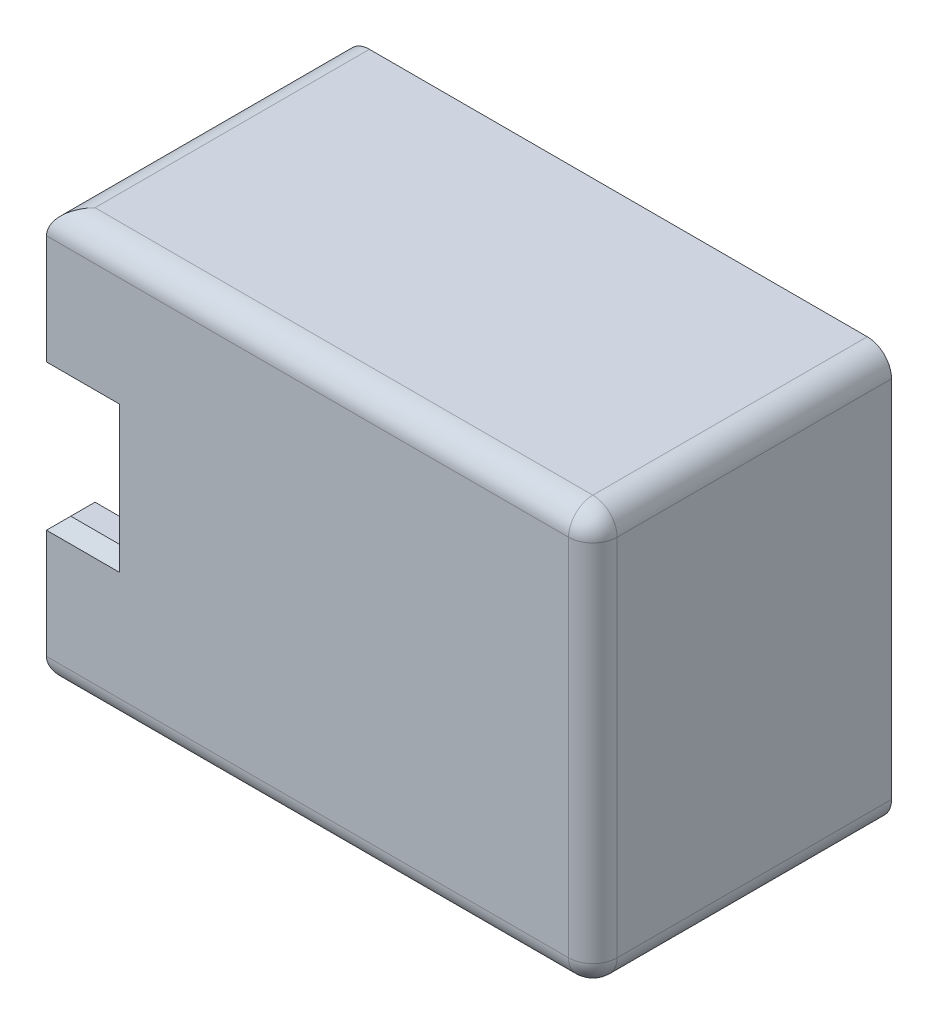
SolidWorks part; units mm, degrees
note: The reader was unsure of these and kept them because the rebuilt part matched: shared geometry of "Sketch1<3>", "Sketch4<4>".
ref_plane "Front Plane" through (0, 0, 0) normal (0, 0, 1) x (1, 0, 0)
ref_plane "Top Plane" through (0, 0, 0) normal (0, 1, 0) x (1, 0, 0)
ref_plane "Right Plane" through (0, 0, 0) normal (1, 0, 0) x (0, 0, -1)
sketch "Sketch1" plane through (0, 0, 0) normal (0, 0, 1) x (1, 0, 0)
  line L0 (-28.575, 17.78) -> (24.765, 17.78)
  line L1 (28.575, -21.59) -> (-28.575, -21.59)
  line L2 (28.575, -21.59) -> (28.575, 21.59)
  line L3 (28.575, 21.59) -> (-28.575, 21.59)
  line L4 (-28.575, -21.59) -> (-28.575, 21.59)
  line L5 (28.575, -21.59) -> (-28.575, 21.59) construction
  line L6 (28.575, 21.59) -> (-28.575, -21.59) construction
  line L7 (24.765, 17.78) -> (24.765, -17.78)
  line L8 (24.765, -17.78) -> (-28.575, -17.78)
  line L9 (-28.575, 10.16) -> (17.145, 10.16)
  line L10 (17.145, 10.16) -> (17.145, -10.16)
  line L11 (17.145, -10.16) -> (-28.575, -10.16)
  point P0 (0, 0)
  dimension "D1" = 57.15
  dimension "D2" = 43.18
  dimension "D3" = 53.34
  dimension "D4" = 35.56
  dimension "D5" = 3.81
  dimension "D6" = 45.72
  dimension "D7" = 20.32
  dimension "D8" = 7.62
extrude "Boss-Extrude1" add sketch "Sketch1" along normal blind 27.432 contours L7 L8 L4 L1 L2 L3 L0
extrude "Boss-Extrude2" add sketch "Sketch1<3>" along normal blind 5.08 contours L10 L11 L4 L8 L7 L0 L9
sketch "Sketch1<3>" plane through (0, 0, 0) normal (0, 0, 1) x (1, 0, 0) same geometry as "Sketch1"
sketch "Sketch4" plane through (0, 0, 5.08) normal (0, 0, 1) x (1, 0, 0)
  line L0 (-28.575, 17.78) -> (24.765, 17.78) construction
  line L1 (-20.6559, 17.78) -> (-23.7941, 17.78)
  line L2 (-23.7941, 17.78) -> (-25.3632, 15.0622)
  line L3 (-25.3632, 15.0622) -> (-23.7941, 12.3444)
  line L4 (-23.7941, 12.3444) -> (-20.6559, 12.3444)
  line L5 (-20.6559, 12.3444) -> (-19.0868, 15.0622)
  line L6 (-19.0868, 15.0622) -> (-20.6559, 17.78)
  line L7 (-28.575, 10.16) -> (-28.575, 17.78) construction
  line L8 (-2.54, 22.7847) -> (-2.54, -11.3368) construction
  line L9 (18.7141, 12.3444) -> (15.5759, 12.3444)
  line L10 (15.5759, 12.3444) -> (14.0068, 15.0622)
  line L11 (14.0068, 15.0622) -> (15.5759, 17.78)
  line L12 (15.5759, 17.78) -> (18.7141, 17.78)
  line L13 (18.7141, 17.78) -> (20.2832, 15.0622)
  line L14 (20.2832, 15.0622) -> (18.7141, 12.3444)
  line L15 (0, 0) -> (10.9329, 0) construction
  line L16 (20.2832, -15.0622) -> (18.7141, -12.3444)
  line L17 (18.7141, -17.78) -> (20.2832, -15.0622)
  line L18 (15.5759, -17.78) -> (18.7141, -17.78)
  line L19 (14.0068, -15.0622) -> (15.5759, -17.78)
  line L20 (15.5759, -12.3444) -> (14.0068, -15.0622)
  line L21 (18.7141, -12.3444) -> (15.5759, -12.3444)
  line L22 (-25.3632, -15.0622) -> (-23.7941, -12.3444)
  line L23 (-23.7941, -17.78) -> (-25.3632, -15.0622)
  line L24 (-19.0868, -15.0622) -> (-20.6559, -17.78)
  line L25 (-20.6559, -12.3444) -> (-19.0868, -15.0622)
  line L26 (-23.7941, -12.3444) -> (-20.6559, -12.3444)
  line L27 (-20.6559, -17.78) -> (-23.7941, -17.78)
  circle A0 centre (-22.225, 15.0622) radius 2.7178 construction
  circle A1 centre (-22.225, 15.0622) radius 1.524
  circle A2 centre (17.145, 15.0622) radius 1.524
  circle A3 centre (-22.225, -15.0622) radius 1.524
  circle A4 centre (17.145, -15.0622) radius 1.524
  dimension "D4" = 3.048
  dimension "D1" = 5.4356
  dimension "D2" = 6.35
  dimension "D3" = 2.54
extrude "Cut-Extrude1" cut sketch "Sketch4" against normal blind 2.286 contours L5 L6 L14 L2 L3 L4 A1 | L14 L13 L11 L10 L9 A2 | L26 L22 L23 L12 L24 L25 A3 | L16 L21 L20 L19 L12 L17 A4
extrude "Cut-Extrude2" cut sketch "Sketch4<4>" against normal through all contours A1 | A2 | A3 | A4
sketch "Sketch4<4>" plane through (0, 0, 5.08) normal (0, 0, 1) x (1, 0, 0) same geometry as "Sketch4"
sketch "Sketch7" plane through (0, 0, 27.432) normal (0, 0, 1) x (1, 0, 0)
  line L0 (0, 0) -> (-22.225, 0) construction
  line L1 (-28.575, 21.59) -> (28.575, 21.59)
  line L2 (-28.575, 21.59) -> (-28.575, 6.35)
  line L3 (-28.575, -21.59) -> (28.575, -21.59)
  line L4 (28.575, 21.59) -> (28.575, -21.59)
  line L5 (-28.575, 6.35) -> (-22.225, 6.35)
  line L7 (-28.575, -6.35) -> (-22.225, -6.35)
  line L8 (-22.225, 6.35) -> (-22.225, -6.35)
  line L9 (-28.575, -6.35) -> (-28.575, -21.59)
  line L10 (-28.575, 0) -> (-1035.3573, 0) construction
  point P11 (-22.225, 0)
  dimension "D1" = 12.7
  dimension "D2" = 6.35
extrude "Boss-Extrude3" add sketch "Sketch7" along normal blind 3.81
fillet "Fillet1" radius 2.54 7 edges at (-28.575, 21.59, 15.621) (28.575, 21.59, 15.621) (28.575, -21.59, 15.621) (-28.575, -21.59, 15.621) (0, -21.59, 31.242) (28.575, 0, 31.242) (0, 21.59, 31.242)
chamfer "Chamfer3" distance 1.27 angle 45 11 edges at (-28.575, 12.065, 27.432) (-28.575, 17.78, 16.256) (-28.575, 6.35, 29.337) (-28.575, -12.065, 27.432) (-28.575, -6.35, 29.337) (-25.4, 6.35, 31.242) (-22.225, 0, 31.242) (-25.4, -6.35, 31.242) (-28.575, -17.78, 16.256) (-28.575, -13.97, 5.08) (-28.575, 13.97, 5.08)
chamfer "Chamfer4" distance 0.254 angle 45 4 edges at (-20.701, -15.0622, 0) (18.669, -15.0622, 0) (-20.701, 15.0622, 0) (18.669, 15.0622, 0)
